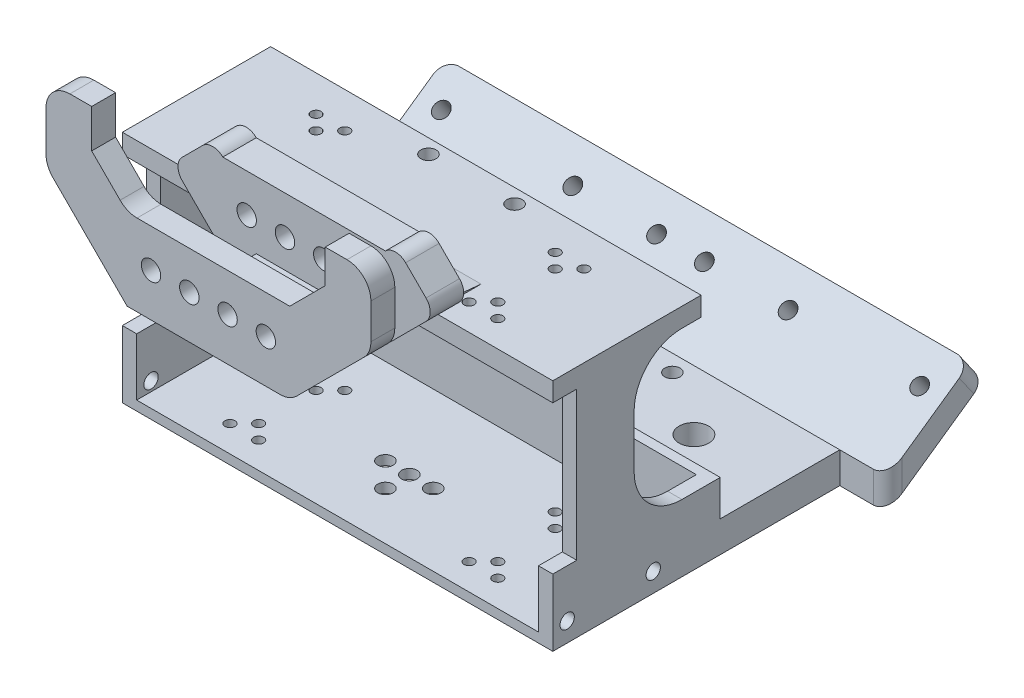
SolidWorks part; units mm, degrees
ref_plane "前视基准面" through (0, 0, 0) normal (0, 0, 1) x (1, 0, 0)
ref_plane "上视基准面" through (0, 0, 0) normal (0, 1, 0) x (1, 0, 0)
ref_plane "右视基准面" through (0, 0, 0) normal (1, 0, 0) x (0, 0, -1)
other "Configuration Table"
sketch "草图1" plane through (0, 0, 0) normal (0, 1, 0) x (1, 0, 0)
  line L1 (-45, 23) -> (45, 23)
  line L2 (-45, 23) -> (-45, -23)
  line L3 (-45, -23) -> (45, -23)
  line L4 (45, 23) -> (45, -23)
  line L5 (-45, 23) -> (45, -23) construction
  line L6 (-45, -23) -> (45, 23) construction
  point P0 (0, 0)
  dimension "D1" = 90
  dimension "D2" = 46
extrude "凸台-拉伸1" add sketch "草图1" along normal blind 4
sketch "草图3" plane through (0, 0, 23) normal (0, 0, 1) x (1, 0, 0)
  line L0 (-45, 0) -> (45, 0) construction
  line L1 (-17, 0) -> (17, 0)
  line L2 (-17, 0) -> (-17, 17) construction
  line L3 (17, 0) -> (17, 17) construction
  line L4 (-17, 17) -> (17, 17)
  line L6 (17, 0) -> (27.6066, 10.6066)
  line L7 (17, 17) -> (19.1066, 19.1066)
  line L9 (27.6066, 10.6066) -> (19.1066, 19.1066)
  line L10 (0, 0) -> (0, 17) construction
  line L11 (-17, 17) -> (-19.1066, 19.1066)
  line L12 (-27.6066, 10.6066) -> (-19.1066, 19.1066)
  line L13 (-17, 0) -> (-27.6066, 10.6066)
  point P0 (-17, 0)
  point P1 (17, 0)
  dimension "D1" = 17
  dimension "D2" = 17
  dimension "D3" = 17
  dimension "D4" = 45
  dimension "D5" = 15
extrude "凸台-拉伸2" add sketch "草图3" along normal blind 7
sketch "草图4" plane through (0, 0, 30) normal (0, 0, 1) x (1, 0, 0)
  line L0 (-18.5, 1.5) -> (18.5, 1.5) construction
  line L1 (-17, 0) -> (17, 0) construction
  line L3 (-27.6066, 10.6066) -> (-17, 0) construction
  line L4 (-10, 3) -> (10, 3)
  line L9 (17, 0) -> (27.6066, 10.6066) construction
  line L10 (-10, 3) -> (-10, 0)
  line L11 (-10, 0) -> (10, 0)
  line L12 (10, 3) -> (10, 0)
  line L13 (-10, 3) -> (10, 0) construction
  line L14 (-10, 0) -> (10, 3) construction
  point P8 (0, 1.5)
  dimension "D1" = 1.5
  dimension "D2" = 20
extrude "凸台-拉伸3" add sketch "草图4" along normal blind 15
sketch "草图5" plane through (0, 0, 45) normal (0, 0, 1) x (1, 0, 0)
  line L4 (-33.9632, 25.4632) -> (-33.9632, 32.4632)
  line L6 (-17, 0) -> (-27.6066, 10.6066)
  line L7 (-27.6066, 10.6066) -> (-17, 0) construction
  line L9 (-19.1066, 19.1066) -> (-17, 17)
  line L10 (-33.9632, 32.4632) -> (-24.4099, 32.4632)
  line L11 (-24.4099, 32.4632) -> (-24.4099, 24.4099)
  line L12 (-17, 17) -> (17, 17)
  line L13 (17, 17) -> (19.1066, 19.1066)
  line L16 (27.6066, 10.6066) -> (17, 0)
  line L17 (17, 0) -> (-17, 0)
  line L19 (-27.6066, 10.6066) -> (-38.2132, 21.2132) construction
  line L20 (-19.1066, 19.1066) -> (-29.7132, 29.7132) construction
  line L21 (-38.2132, 21.2132) -> (-29.7132, 29.7132) construction
  line L23 (19.1066, 19.1066) -> (29.7132, 29.7132) construction
  line L24 (27.6066, 10.6066) -> (38.2132, 21.2132) construction
  line L25 (29.7132, 29.7132) -> (38.2132, 21.2132) construction
  line L27 (24.4099, 24.4099) -> (24.4099, 31.4099)
  line L28 (24.4099, 31.4099) -> (33.9632, 31.4099)
  line L29 (33.9632, 31.4099) -> (33.9632, 25.4632)
  line L30 (-24.4099, 24.4099) -> (-19.1066, 19.1066)
  line L31 (19.1066, 19.1066) -> (24.4099, 24.4099)
  line L33 (-33.9632, 25.4632) -> (-33.9632, 16.9632)
  line L34 (-33.9632, 16.9632) -> (-27.6066, 10.6066)
  line L36 (33.9632, 25.4632) -> (33.9632, 16.9632)
  line L37 (33.9632, 16.9632) -> (27.6066, 10.6066)
  dimension "D1" = 15
  dimension "D2" = 15
  dimension "D3" = 7
  dimension "D4" = 7
extrude "凸台-拉伸4" add sketch "草图5" along normal blind 5
sketch "草图6" plane through (0, 0, 50) normal (0, 0, 1) x (1, 0, 0)
  line L0 (-20, 9) -> (20, 9) construction
  line L2 (-17, 0) -> (17, 0) construction
  circle A0 centre (-12, 9) radius 2.03
  circle A1 centre (-4, 9) radius 2.03
  circle A2 centre (4, 9) radius 2.03
  circle A3 centre (12, 9) radius 2.03
  point P6 (-12, 9)
  point P7 (-4, 9)
  point P8 (4, 9)
  point P9 (12, 9)
  point P10 (0, 9)
  dimension "D5" = 9
  dimension "D1" = 4
  dimension "D2" = 4
  dimension "D3" = 8
  dimension "D4" = 8
extrude "切除-拉伸2" cut sketch "草图6" against normal up to surface (27 mm away) up to face at (0, 12.6783, 23)
sketch "草图8" plane through (0, 0, 23) normal (0, 0, -1) x (-1, 0, 0)
  line L0 (0, 0) -> (0, -12.5)
  line L1 (-45, 0) -> (45, 0) construction
  line L2 (0, -12.5) -> (27, -12.5)
  line L3 (0, -12.5) -> (-27, -12.5)
  dimension "D1" = 12.5
  dimension "D2" = 27
  dimension "D3" = 27
ref_plane "基准面1" through (0, -12.5, 0) normal (0, -1, 0) x (-1, 0, 0)
sketch "草图9" plane through (0, -12.5, 0) normal (0, -1, 0) x (-1, 0, 0)
  line L0 (27, -17) -> (27, -26.6611) construction
  line L1 (-27, -17) -> (-27, -21.8305) construction
sketch "草图11" plane through (0, 0, 0) normal (0, -1, 0) x (1, 0, 0)
  line L0 (-45, 18) -> (-42, 18)
  line L1 (-45, 18) -> (-45, 6)
  line L2 (-42, 18) -> (-42, 6)
  line L3 (-45, 6) -> (-42, 6)
  line L4 (-45, -23) -> (-45, 23) construction
  line L5 (-45, 23) -> (-17, 23) construction
  line L6 (0, 0) -> (0, -23) construction
  line L7 (45, -23) -> (-45, -23) construction
  line L8 (45, 6) -> (42, 6)
  line L9 (42, 18) -> (42, 6)
  line L10 (45, 18) -> (45, 6)
  line L11 (45, 18) -> (42, 18)
  dimension "D1" = 5
  dimension "D2" = 12
  dimension "D3" = 3
extrude "凸台-拉伸5" add sketch "草图11" along normal blind 31
sketch "草图12" plane through (0, -31, 0) normal (0, -1, 0) x (1, 0, 0)
  line L0 (42, -10) -> (42, 23)
  line L9 (-45, 23) -> (-45, -12)
  line L15 (17, 23) -> (45, 23) construction
  line L18 (42, 23) -> (45, 23)
  line L20 (-42, 6) -> (-42, 18) construction
  line L30 (-45, -23) -> (-45, 6) construction
  line L31 (-45, -12) -> (45, -12)
  line L32 (45, 6) -> (45, -23) construction
  line L33 (45, -12) -> (45, 23)
  line L34 (-45, 23) -> (-42, 23)
  line L35 (-45, 23) -> (-17, 23) construction
  line L36 (-42, 23) -> (-42, -10)
  line L37 (-42, -10) -> (42, -10)
  line L38 (42, 18) -> (42, 6) construction
  dimension "D1" = 35
  dimension "D2" = 2
extrude "凸台-拉伸6" add sketch "草图12" along normal blind 12
sketch "草图13" plane through (0, -43, 0) normal (0, -1, 0) x (1, 0, 0)
  line L7 (-45, 23) -> (45, 23)
  line L8 (-45, 23) -> (-45, -12)
  line L9 (-45, -12) -> (45, -12)
  line L10 (45, 23) -> (45, -12)
extrude "凸台-拉伸7" add sketch "草图13" along normal blind 2
sketch "草图14" plane through (0, -45, 0) normal (0, -1, 0) x (1, 0, 0)
  line L0 (0, 8.5) -> (0, -12) construction
  line L2 (0, 8.5) -> (25, 8.5) construction
  line L3 (25, 8.5) -> (25, 14.5) construction
  line L4 (25, 14.5) -> (25, 17.5) construction
  line L5 (25, 17.5) -> (28, 17.5) construction
  line L6 (25, 17.5) -> (22, 17.5) construction
  line L7 (-45, -12) -> (45, -12) construction
  circle A0 centre (22, 17.5) radius 1.05
  circle A1 centre (28, 17.5) radius 1.05
  circle A2 centre (25, 14.5) radius 1.05
  circle A3 centre (22, -0.5) radius 1.05
  circle A4 centre (25, 2.5) radius 1.05
  circle A5 centre (28, -0.5) radius 1.05
  circle A6 centre (-28, -0.5) radius 1.05
  circle A7 centre (-22, -0.5) radius 1.05
  circle A8 centre (-25, 2.5) radius 1.05
  circle A9 centre (-22, 17.5) radius 1.05
  circle A10 centre (-25, 14.5) radius 1.05
  circle A11 centre (-28, 17.5) radius 1.05
  point P0 (0, 8.5)
  dimension "D2" = 6
  dimension "D1" = 25
  dimension "D3" = 3
  dimension "D4" = 3
  dimension "D5" = 3
extrude "切除-拉伸3" cut sketch "草图14" against normal through all both and the other way through all
fillet "圆角3" radius 10 4 edges at (43.5, -31, 6) (-43.5, -31, 6) (43.5, 0, 6) (-43.5, 0, 6)
fillet "圆角5" radius 5 8 edges at (-17, 17, 47.5) (-17, 0, 26.5) (17, 0, 26.5) (17, 0, 47.5) (-33.9632, 32.4632, 47.5) (33.9632, 31.4099, 47.5) (33.9632, 16.9632, 47.5) (-33.9632, 16.9632, 47.5)
fillet "圆角9" radius 3 4 edges at (-27.6066, 10.6066, 26.5) (-19.1066, 19.1066, 26.5) (19.1066, 19.1066, 26.5) (27.6066, 10.6066, 26.5)
sketch "草图16" plane through (0, 4, 0) normal (0, 1, 0) x (1, 0, 0)
  line L0 (45, -23) -> (45, 23) construction
  line L1 (-45, 23) -> (45, 23)
  line L2 (-45, 23) -> (-45, 8)
  line L3 (-45, 8) -> (45, 8)
  line L4 (45, 23) -> (45, 8)
  dimension "D1" = 15
extrude "切除-拉伸4" cut sketch "草图16" against normal up to next
sketch "草图17" plane through (0, 0, -12) normal (0, 0, -1) x (-1, 0, 0)
  line L0 (45, -45) -> (45, -31) construction
  line L1 (-45, -45) -> (45, -45)
  line L2 (-45, -45) -> (-45, -38.5)
  line L3 (-45, -38.5) -> (45, -38.5)
  line L4 (45, -45) -> (45, -38.5)
  dimension "D1" = 6.5
extrude "凸台-拉伸8" add sketch "草图17" along normal blind 25
sketch "草图22" plane through (0, -45, 0) normal (0, -1, 0) x (1, 0, 0)
  line L0 (0, 23) -> (0, 13) construction
  line L1 (45, 23) -> (-45, 23) construction
  circle A0 centre (0, 13) radius 1.6
  circle A1 centre (5, 8) radius 1.6
  circle A2 centre (0, 8) radius 1.6
  circle A3 centre (-5, 8) radius 1.6
  point P5 (0, 8)
  point P6 (5, 8)
  point P7 (-5, 8)
  dimension "D1" = 10
  dimension "D2" = 5
  dimension "D3" = 5
  dimension "D4" = 5
extrude "切除-拉伸6" cut sketch "草图22" against normal up to next
sketch "草图25" plane through (0, 0, 0) normal (0, -1, 0) x (1, 0, 0)
  line L0 (0, 0) -> (0, -10.2866) construction
  line L1 (45, -8) -> (-45, -8) construction
  line L2 (45, -8) -> (45, 23) construction
  line L3 (45, 23) -> (-45, 23) construction
  line L4 (-45, -8) -> (-45, 23) construction
  line L5 (9, -5) -> (-9, -5) construction
  line L6 (9, -5) -> (9, 22) construction
  line L7 (9, 22) -> (-9, 22) construction
  line L8 (-9, -5) -> (-9, 22) construction
  circle A0 centre (-9, 22) radius 1.6
  circle A1 centre (9, 22) radius 1.6
  circle A2 centre (9, -5) radius 1.6
  circle A3 centre (-9, -5) radius 1.6
  point P4 (0, -4)
  point P5 (9, -5)
  point P18 (0, -5)
  dimension "D1" = 3
  dimension "D3" = 27
  dimension "D4" = 18
extrude "切除-拉伸7" cut sketch "草图25" against normal up to surface (4 mm away) up to face at (0, 4, 12.6667)
sketch "草图28" plane through (0, 0, 0) normal (1, 0, 0) x (0, 0, -1)
  line L0 (-23, 4) -> (-13, 4)
  line L1 (-23, 4) -> (8, 4) construction
  line L2 (-13, 4) -> (-23, 5)
  line L3 (-23, 4) -> (-23, 8.4853) construction
  line L4 (-23, 5) -> (-23, 4)
  dimension "D1" = 1
  dimension "D2" = 10
extrude "凸台-拉伸10" add sketch "草图28" along normal mid plane 40
sketch "草图29" plane through (0, 0, 0) normal (1, 0, 0) x (0, 0, -1)
  line L0 (37, -38.5) -> (54.4248, -26.299)
  line L1 (54.4248, -26.299) -> (57.4788, -30.6606)
  line L2 (57.4788, -30.6606) -> (37, -45)
  line L3 (37, -38.5) -> (37, -45)
  line L4 (33.2326, -45) -> (47.1106, -45) construction
  dimension "D1" = 25
  dimension "D2" = 55
extrude "凸台-拉伸11" add sketch "草图29" along normal mid plane 110
sketch "草图31" plane through (0, -47.5798, -33.3157) normal (0, -0.8192, -0.5736) x (1, 0, 0)
  line L0 (55, -4.4977) -> (45, -4.4977) construction
  line L1 (-55, -29.4977) -> (55, -29.4977) construction
  line L2 (-55, -29.4977) -> (-55, -4.4977) construction
  line L3 (-55, -4.4977) -> (55, -4.4977) construction
  line L4 (55, -29.4977) -> (55, -4.4977) construction
  line L5 (0, -4.4977) -> (0, -29.4977) construction
  line L6 (-55, -22.4977) -> (55, -22.4977) construction
  line L7 (55, -4.4977) -> (55, -29.4977) construction
  circle A0 centre (-50, -22.4977) radius 1.6
  circle A1 centre (-5, -22.4977) radius 1.6
  circle A2 centre (5, -22.4977) radius 1.6
  circle A3 centre (50, -22.4977) radius 1.6
  circle A4 centre (-22.5, -22.4977) radius 1.6
  circle A5 centre (22.5, -22.4977) radius 1.6
  point P11 (5, -22.4977)
  point P12 (50, -22.4977)
  point P13 (-5, -22.4977)
  point P14 (-50, -22.4977)
  point P116 (0, -16.9977)
  dimension "D6" = 22.5
  dimension "D1" = 7
  dimension "D2" = 5
  dimension "D3" = 45
  dimension "D4" = 5
  dimension "D5" = 45
  dimension "D7" = 22.5
extrude "切除-拉伸8" cut sketch "草图31" against normal up to next
sketch "草图32" plane through (0, -38.5, 0) normal (0, 1, 0) x (1, 0, 0)
  line L1 (-45, 37) -> (45, 37) construction
  line L2 (-45, 37) -> (-45, 12) construction
  line L3 (-45, 12) -> (45, 12) construction
  line L4 (45, 37) -> (45, 12) construction
  line L5 (0, 12) -> (0, 37) construction
  line L6 (-45, 24.5) -> (45, 24.5) construction
  line L7 (-13.5, 33.5) -> (13.5, 33.5) construction
  line L8 (-13.5, 33.5) -> (-13.5, 15.5) construction
  line L9 (-13.5, 15.5) -> (13.5, 15.5) construction
  line L10 (13.5, 33.5) -> (13.5, 15.5) construction
  line L11 (-13.5, 33.5) -> (13.5, 15.5) construction
  line L12 (-13.5, 15.5) -> (13.5, 33.5) construction
  circle A0 centre (13.5, 33.5) radius 1.6
  circle A1 centre (13.5, 15.5) radius 1.6
  circle A2 centre (-13.5, 15.5) radius 1.6
  circle A3 centre (-13.5, 33.5) radius 1.6
  circle A4 centre (0, 24.5) radius 3.1
  circle A5 centre (27, 24.5) radius 3.1
  circle A6 centre (-27, 24.5) radius 3.1
  point P4 (0, 24.5)
  point P80 (0, 24.5)
  dimension "D1" = 27
  dimension "D2" = 27
extrude "切除-拉伸9" cut sketch "草图32" against normal up to next
fillet "圆角12" radius 3 4 edges at (55, -41.75, -37) (-55, -41.75, -37) (55, -28.4798, -55.9518) (-55, -28.4798, -55.9518)
sketch "草图33" plane through (45, 0, 0) normal (1, 0, 0) x (0, 0, -1)
  line L0 (37, -45) -> (-23, -45) construction
  line L1 (-23, -45) -> (-23, -31) construction
  circle A0 centre (-2, -41) radius 1.5
  circle A1 centre (-20, -41) radius 1.5
  point P0 (-20, -41)
  dimension "D3" = 18
  dimension "D1" = 4
  dimension "D2" = 3
extrude "切除-拉伸10" cut sketch "草图33" against normal through all
